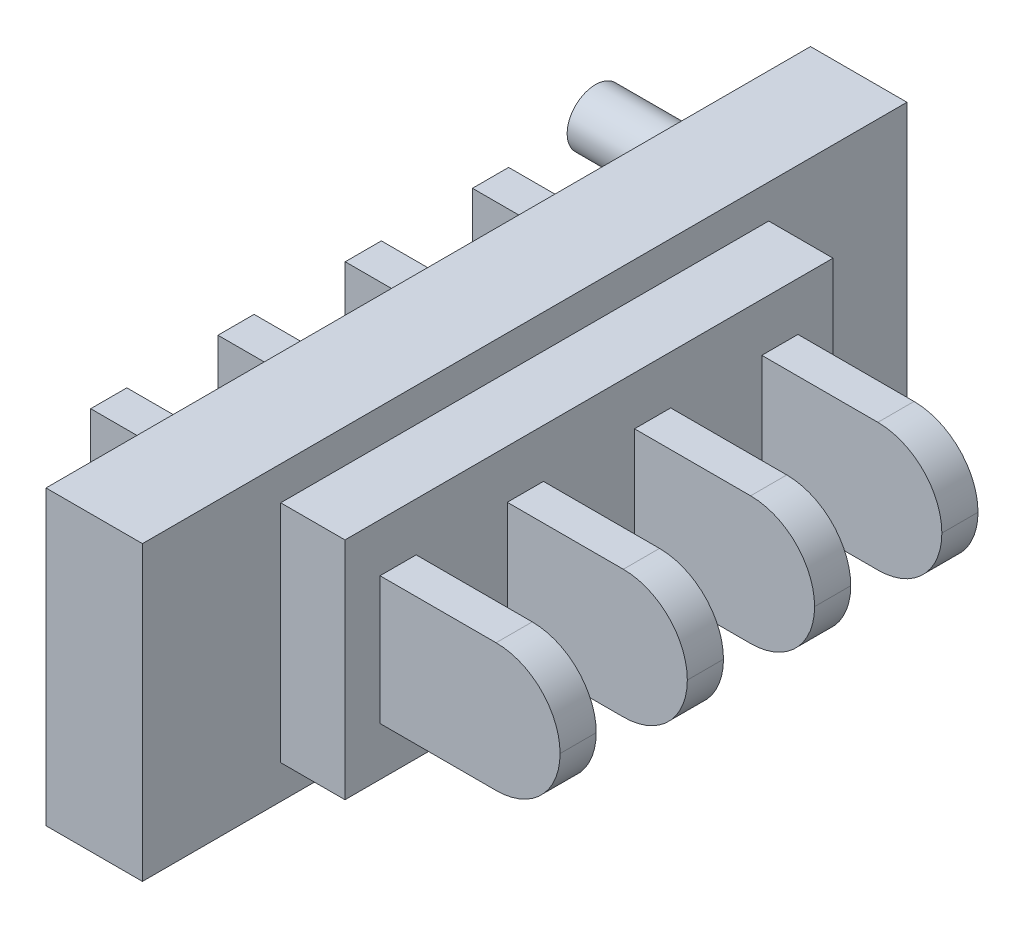
SolidWorks part; units mm, degrees
ref_plane "Plan de face" through (0, 0, 0) normal (0, 0, 1) x (1, 0, 0)
ref_plane "Plan de dessus" through (0, 0, 0) normal (0, 1, 0) x (1, 0, 0)
ref_plane "Plan de droite" through (0, 0, 0) normal (1, 0, 0) x (0, 0, -1)
sketch "Esquisse2" plane through (0, 0, 0) normal (1, 0, 0) x (0, 0, -1)
  line L2 (-11.89, 4.55) -> (-11.89, 0)
  line L3 (-11.89, 0) -> (0, 0)
  line L4 (-11.89, 4.55) -> (0, 4.55)
  line L5 (0, 4.55) -> (0, 0)
  line L6 (-11.89, 0) -> (-3, 0) construction
  dimension "D1" = 4.55
  dimension "D2" = 11.89
extrude "Boss.-Extru.1" add sketch "Esquisse2" along normal blind 1.5
sketch "Esquisse7" plane through (1.5, 0, 0) normal (1, 0, 0) x (0, 0, -1)
  line L0 (-5.945, 4.025) -> (-5.945, 4.55) construction
  line L1 (0, 4.55) -> (-11.89, 4.55) construction
  line L2 (-9.74, 2.275) -> (-11.89, 2.275) construction
  line L3 (-11.89, 4.55) -> (-11.89, 0) construction
  line L7 (-2.15, 0.525) -> (-9.74, 0.525)
  line L8 (-2.15, 0.525) -> (-2.15, 4.025)
  line L9 (-2.15, 4.025) -> (-9.74, 4.025)
  line L10 (-9.74, 0.525) -> (-9.74, 4.025)
  dimension "D1" = 7.59
  dimension "D2" = 3.5
extrude "Boss.-Extru.2" add sketch "Esquisse7" along normal blind 1 contours L8 L7 L10 L9
ref_plane "Plan1" through (5.3, 0, 0) normal (1, 0, 0) x (0, 0, -1)
sketch "Esquisse8" plane through (5.3, 0, 0) normal (1, 0, 0) x (0, 0, -1)
  line L0 (-8.6328, 2.275) -> (-7.2157, 2.275) construction
  line L1 (-7.2157, 2.275) -> (-6.6535, 2.275) construction
  line L3 (-6.6535, 3.27) -> (-7.2157, 3.27)
  line L4 (-2.695, 3.27) -> (-3.2572, 3.27)
  line L5 (-6.6535, 3.27) -> (-6.6535, 1.28)
  line L6 (-2.695, 3.27) -> (-2.695, 1.28)
  line L7 (-6.6535, 1.28) -> (-7.2157, 1.28)
  line L8 (-9.195, 1.28) -> (-9.195, 3.27)
  line L10 (-2.695, 1.28) -> (-2.695, 3.27)
  line L11 (-2.695, 1.28) -> (-3.2572, 1.28)
  line L12 (-3.2572, 3.27) -> (-3.2572, 1.28)
  line L17 (-9.195, 3.27) -> (-8.6328, 3.27)
  line L18 (-9.195, 3.27) -> (-9.195, 1.28)
  line L19 (-9.195, 1.28) -> (-8.6328, 1.28)
  line L20 (-8.6328, 3.27) -> (-8.6328, 1.28)
  line L21 (-7.2157, 3.27) -> (-7.2157, 1.28)
  line L22 (-4.6743, 3.27) -> (-5.2365, 3.27)
  line L23 (-4.6743, 3.27) -> (-4.6743, 1.28)
  line L24 (-4.6743, 1.28) -> (-5.2365, 1.28)
  line L25 (-5.2365, 3.27) -> (-5.2365, 1.28)
  line L26 (-6.6535, 2.275) -> (-5.2365, 2.275) construction
  line L27 (-5.2365, 2.275) -> (-4.6743, 2.275) construction
  line L28 (-4.6743, 2.275) -> (-3.2572, 2.275) construction
  line L29 (-5.945, 2.275) -> (-5.945, 4.025) construction
  line L30 (-2.15, 4.025) -> (-9.74, 4.025) construction
  line L31 (-5.945, 2.275) -> (-5.945, 0.525) construction
  line L32 (-2.15, 0.525) -> (-9.74, 0.525) construction
  dimension "D1" = 1.99
  dimension "D2" = 0.5622
  dimension "D3" = 6.5
extrude "Boss.-Extru.4" add sketch "Esquisse8" against normal blind 7.3 contours L5 L3 L21 L7 | L23 L22 L25 L24 | L18 L17 L20 L19 | L6 L4 L12 L11
fillet "Congé6" radius 0.995 8 edges at (5.3, 1.28, 2.9761) (5.3, 1.28, 4.9554) (5.3, 1.28, 6.9346) (5.3, 1.28, 8.9139) (5.3, 3.27, 8.9139) (5.3, 3.27, 6.9346) (5.3, 3.27, 4.9554) (5.3, 3.27, 2.9761)
sketch "Esquisse12" plane through (0, 0, 0) normal (-1, 0, 0) x (0, 0, 1)
  line L0 (5.945, 4.55) -> (5.945, 0) construction
  line L1 (0, 4.55) -> (11.89, 4.55) construction
  line L2 (11.89, 0) -> (0, 0) construction
  line L3 (5.945, 0) -> (9.755, 0) construction
  line L4 (9.755, 0) -> (9.755, 0.49) construction
  line L5 (5.945, 4.55) -> (2.135, 4.55) construction
  line L6 (2.135, 4.55) -> (2.135, 4.06) construction
  line L8 (9.195, 3.27) -> (9.195, 1.28) construction
  circle A0 centre (2.135, 4.06) radius 0.44
  circle A1 centre (9.755, 0.49) radius 0.44
  dimension "D1" = 0.88
  dimension "D2" = 7.06
  dimension "D3" = 0.49
extrude "Boss.-Extru.5" add sketch "Esquisse12" along normal blind 1.21
equation "\"D2@Esquisse12\"=7.5-0.88/2"
